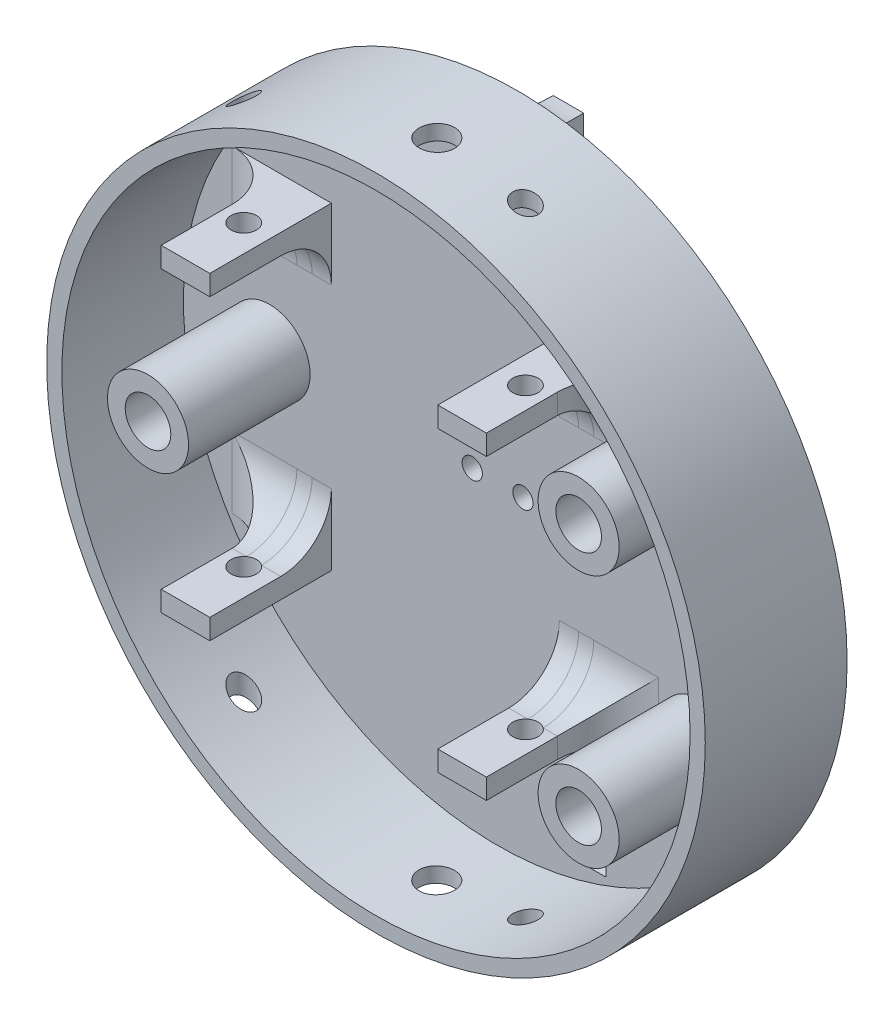
SolidWorks part; units mm, degrees
ref_plane "Alzado" through (0, 0, 0) normal (0, 0, 1) x (1, 0, 0)
ref_plane "Planta" through (0, 0, 0) normal (0, 1, 0) x (1, 0, 0)
ref_plane "Vista lateral" through (0, 0, 0) normal (1, 0, 0) x (0, 0, -1)
sketch "Croquis1" plane through (0, 0, 0) normal (0, 0, 1) x (1, 0, 0)
  line L0 (10, 20) -> (-10, 20) construction
  circle A0 centre (0, 0) radius 32.5
  circle A1 centre (-2.5, 0) radius 1
  circle A2 centre (2.5, 0) radius 1
  circle A3 centre (0, 20) radius 1
  circle A4 centre (10, 20) radius 1
  circle A5 centre (-10, 20) radius 1
  point P9 (0, 20)
  dimension "D1" = 65
  dimension "D4" = 2
  dimension "D7" = 2
  dimension "D2" = 2.5
  dimension "D3" = 2.5
  dimension "D5" = 20
  dimension "D6" = 20
extrude "Saliente-Extruir1" add sketch "Croquis1" along normal blind 2
sketch "Croquis2" plane through (0, 0, 2) normal (0, 0, 1) x (1, 0, 0)
  line L0 (-21.2, -15.7) -> (-16.4, -15.7)
  line L1 (10.9, -15.7) -> (6.1, -15.7)
  line L2 (-21.2, -15.7) -> (-21.2, -13.7)
  line L3 (-21.2, -13.7) -> (-16.4, -13.7)
  line L4 (-16.4, -13.7) -> (-16.4, -15.7)
  line L5 (6.1, -15.7) -> (6.1, -13.7)
  line L6 (6.1, -13.7) -> (10.9, -13.7)
  line L7 (10.9, -13.7) -> (10.9, -15.7)
  line L8 (6.1, -15.7) -> (10.9, -15.7)
  line L9 (0, 0) -> (12.8027, 0) construction
  line L10 (10.9, 13.7) -> (10.9, 15.7)
  line L11 (10.9, 15.7) -> (6.1, 15.7)
  line L12 (6.1, 13.7) -> (10.9, 13.7)
  line L13 (6.1, 15.7) -> (6.1, 13.7)
  line L14 (-16.4, 13.7) -> (-16.4, 15.7)
  line L15 (-21.2, 15.7) -> (-16.4, 15.7)
  line L16 (-21.2, 15.7) -> (-21.2, 13.7)
  line L17 (-21.2, 13.7) -> (-16.4, 13.7)
  point P2 (0, -15.7)
  point P3 (-16.4, -15.7)
  point P13 (8.5, -15.7)
  point P16 (8.5, 15.7)
  dimension "D1" = 32.1
  dimension "D2" = 10.9
  dimension "D3" = 15.7
  dimension "D4" = 4.8
  dimension "D5" = 4.8
  dimension "D6" = 2
  dimension "D7" = 2
extrude "Saliente-Extruir2" add sketch "Croquis2" along normal blind 12 contours L7 L6 L5 L1 | L4 L3 L2 L0 | L16 L17 L14 L15 | L11 L13 L12 L10 region at (-18.8, -14.7, 2) region at (8.5, -14.7, 2) region at (8.5, 14.7, 2) region at (-18.8, 14.7, 2)
sketch "Croquis3" plane through (0, -15.7, 0) normal (0, -1, 0) x (1, 0, 0)
  line L0 (-21.2, 14) -> (-21.2, 2) construction
  line L3 (10.9, 14) -> (10.9, 2) construction
  line L6 (-21.2, 2) -> (-16.4, 2) construction
  circle A0 centre (-19.05, 8) radius 1.25
  circle A1 centre (8.75, 8) radius 1.25
  dimension "D1" = 2.5
  dimension "D2" = 2.15
  dimension "D3" = 2.15
  dimension "D4" = 6
extrude "Cortar-Extruir1" cut sketch "Croquis3" against normal up to surface (31.4 mm away) up to face at (8.5, 15.7, 8)
ref_plane "Plano1" through (0, -32.5, 0) normal (0, -1, 0) x (-1, 0, 0)
ref_plane "Plano2" through (0, -28.35, 0) normal (0, -1, 0) x (-1, 0, 0)
sketch "Croquis5" plane through (0, -28.35, 0) normal (0, -1, 0) x (-1, 0, 0)
  line L0 (-8.75, -8) -> (19.05, -8) construction
  line L1 (0, 0) -> (0, -8) construction
  line L2 (-32.5, -2) -> (32.5, -2) construction
  line L3 (-10.68, -2) -> (-8.3104, -2)
  line L4 (32.5, 0) -> (-32.5, 0) construction
  line L5 (9.277, 0) -> (6.408, 0)
  line L6 (8.3104, -2) -> (10.68, -2)
  line L7 (-6.408, 0) -> (-9.277, 0)
  arc A0 (-9.277, 0) -> (-10.68, -2) centre (0, -8) ccw
  arc A1 (-6.408, 0) -> (-8.3104, -2) centre (0, -8) ccw
  arc A2 (10.68, -2) -> (9.277, 0) centre (0, -8) ccw
  arc A3 (8.3104, -2) -> (6.408, 0) centre (0, -8) ccw
  dimension "D1" = 24.5
  dimension "D2" = 20.5
extrude "Cortar-Extruir3" cut sketch "Croquis5" against normal blind 2
mirror "Simetría1" about plane through (0, 0, 0) normal (0, 1, 0) of "Cortar-Extruir3"
sketch "Croquis6" plane through (0, 0, 0) normal (0, 0, -1) x (-1, 0, 0)
  circle A0 centre (-20, 12.5) radius 2.25
  circle A1 centre (-20, -12.5) radius 2.25
  circle A2 centre (22.5, 0) radius 2.25
  dimension "D1" = 4.5
  dimension "D2" = 4.5
  dimension "D3" = 4.5
  dimension "D6" = 25
  dimension "D7" = 12.5
  dimension "D4" = 22.5
  dimension "D5" = 20
extrude "Cortar-Extruir4" cut sketch "Croquis6" against normal blind 2.5
sketch "Croquis7" plane through (0, 0, 2) normal (0, 0, 1) x (1, 0, 0)
  circle A2 centre (0, 0) radius 32.5 construction
  circle A9 centre (0, 0) radius 32.5
  circle A11 centre (0, 0) radius 31
  dimension "D1" = 1.5
extrude "Saliente-Extruir3" add sketch "Croquis7" along normal blind 12
ref_plane "Plano3" through (0, -32.5, 0) normal (0, -1, 0) x (-1, 0, 0)
sketch "Croquis8" plane through (0, -32.5, 0) normal (0, -1, 0) x (-1, 0, 0)
  circle A0 centre (-8.75, -8) radius 1.25 construction
  circle A1 centre (-8.75, -8) radius 1.25
  circle A2 centre (19.05, -8) radius 1.25 construction
  circle A3 centre (19.05, -8) radius 1.25
  circle A4 centre (0, -8) radius 1.75
  dimension "D1" = 3.5
extrude "Cortar-Extruir5" cut sketch "Croquis8" against normal blind 70
sketch "Sketch1" plane through (0, 0, 0) normal (0, 0, -1) x (-1, 0, 0)
  line L0 (6.408, 26.35) -> (6.408, 28.35) construction
  line L1 (-1.502, 28.85) -> (1.498, 28.85)
  line L2 (-1.502, 28.85) -> (-1.502, 25.85)
  line L3 (-1.502, 25.85) -> (1.498, 25.85)
  line L4 (1.498, 28.85) -> (1.498, 25.85)
  line L5 (-1.502, 28.85) -> (1.498, 25.85) construction
  line L6 (-1.502, 25.85) -> (1.498, 28.85) construction
  line L7 (0, 0) -> (-11.4103, 0) construction
  line L8 (-1.502, -25.85) -> (1.498, -28.85) construction
  line L9 (-1.502, -28.85) -> (1.498, -25.85) construction
  line L10 (1.498, -28.85) -> (1.498, -25.85)
  line L11 (-1.502, -25.85) -> (1.498, -25.85)
  line L12 (-1.502, -28.85) -> (-1.502, -25.85)
  line L13 (-1.502, -28.85) -> (1.498, -28.85)
  line L14 (-6.408, -26.35) -> (-6.408, -28.35) construction
  point P0 (-0.002, 27.35)
  point P8 (6.408, 27.35)
  point P15 (-0.002, -27.35)
  dimension "D1" = 4.91
  dimension "D2" = 3
  dimension "D3" = 3
  dimension "D4" = 4.906
extrude "Boss-Extrude1" add sketch "Sketch1" along normal blind 5
fillet "Fillet1" radius 2 6 edges at (1.502, 27.35, 0) (-1.498, -27.35, 0) (0.002, 25.85, 0) (0.002, 28.85, 0) (0.002, -25.85, 0) (0.002, -28.85, 0) second distance 5 first distance on face at (0.002, 27.35, 0)
sketch "Sketch2" plane through (0, 0, 2) normal (0, 0, 1) x (1, 0, 0)
  line L1 (-10.68, -26.35) -> (-5.6668, -26.35)
  line L2 (-10.68, -26.35) -> (-10.68, -28.75)
  line L3 (-10.68, -28.75) -> (-5.6668, -28.75)
  line L4 (-5.6668, -26.35) -> (-5.6668, -28.75)
  line L5 (10.68, 26.35) -> (5.4941, 26.35)
  line L6 (10.68, 26.35) -> (10.68, 28.75)
  line L7 (10.68, 28.75) -> (5.4941, 28.75)
  line L8 (5.4941, 26.35) -> (5.4941, 28.75)
extrude "Tapon" add sketch "Sketch2" against normal up to surface (2 mm away) up to face at (1.002, 25.6, 0)
fillet "Fillet4" radius 5 8 edges at (-21.2, 14.7, 2) (-21.2, -14.7, 2) (-18.8, -13.7, 2) (-18.8, 13.7, 2) (10.9, 14.7, 2) (8.5, 13.7, 2) (8.5, -13.7, 2) (10.9, -14.7, 2)
sketch "Croquis9" plane through (0, 0, 2) normal (0, 0, 1) x (1, 0, 0)
  circle A0 centre (20, -12.5) radius 2.25 construction
  circle A1 centre (20, -12.5) radius 2.25
  circle A2 centre (-22.5, 0) radius 2.25 construction
  circle A3 centre (-22.5, 0) radius 2.25
  circle A4 centre (20, 12.5) radius 2.25 construction
  circle A5 centre (20, 12.5) radius 2.25
  circle A6 centre (-22.5, 0) radius 4
  circle A7 centre (20, -12.5) radius 4
  circle A8 centre (20, 12.5) radius 4
  dimension "D1" = 8
extrude "Saliente-Extruir4" add sketch "Croquis9" along normal up to surface (12 mm away) up to face at (32.5, 0, 14)
equation "\"D2@Croquis6\"=\"D1@Croquis6\""
equation "\"D3@Croquis6\"=\"D1@Croquis6\""
equation "\"D7@Croquis6\"=\"D6@Croquis6\"/2"
